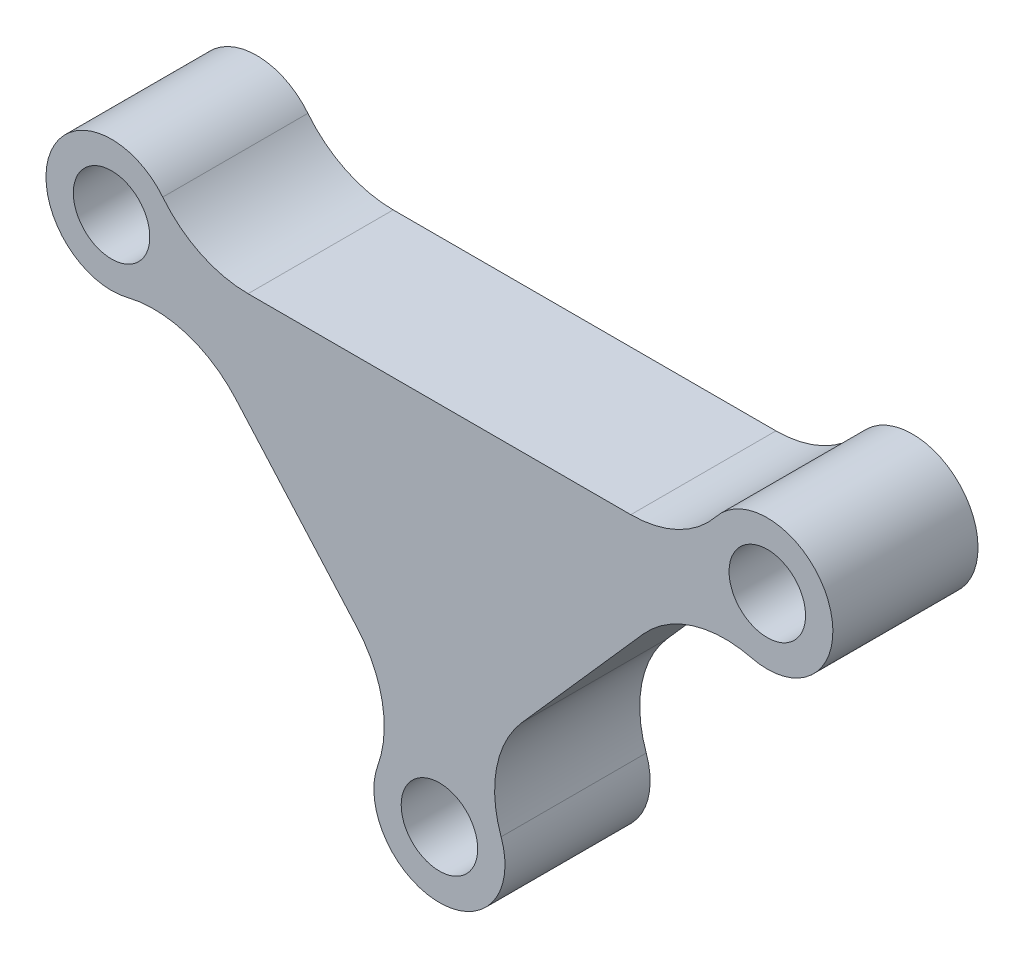
SolidWorks part; units mm, degrees
ref_plane "Plan de face" through (0, 0, 0) normal (0, 0, 1) x (1, 0, 0)
ref_plane "Plan de dessus" through (0, 0, 0) normal (0, 1, 0) x (1, 0, 0)
ref_plane "Plan de droite" through (0, 0, 0) normal (1, 0, 0) x (0, 0, -1)
sketch "Esquisse2" plane through (0, 0, 0) normal (0, 0, 1) x (1, 0, 0)
  line L0 (-13.25, 10) -> (13.25, 10)
  line L1 (13.25, 10) -> (0, -5)
  line L2 (0, -5) -> (-13.25, 10)
  line L3 (0, 0) -> (-13.25, 10) construction
  line L4 (0, 0) -> (13.25, 10) construction
  circle A0 centre (-15, 10) radius 3
  circle A1 centre (-15, 10) radius 1.75
  circle A2 centre (15, 10) radius 3
  circle A3 centre (15, 10) radius 1.75
  circle A4 centre (0, -6.75) radius 3
  circle A5 centre (0, -6.75) radius 1.75
  dimension "D2" = 3.5
  dimension "D3" = 6
  dimension "D1" = 5
  dimension "D4" = 10
  dimension "D5" = 15
extrude "Boss.-Extru.1" add sketch "Esquisse2" along normal blind 6.64 contours A4 L1 A2 L0 A0 L2 | L1 A5 L2 A4 | L1 A4 L2 | A3 | A1 | L0 L1 L2 | A2 | A0 | A4 | A5 region at (-15, 10, 0) region at (0, 5.023, 0) region at (15, 10, 0) region at (0, -4.2028, 0) region at (-0.5446, -4.5099, 0)
fillet "Congé1" radius 5 6 edges at (-12, 10, 3.32) (-12.2308, 8.8462, 3.32) (-0.9637, -3.909, 3.32) (12.2308, 8.8462, 3.32) (12, 10, 3.32) (0.9637, -3.909, 3.32)
